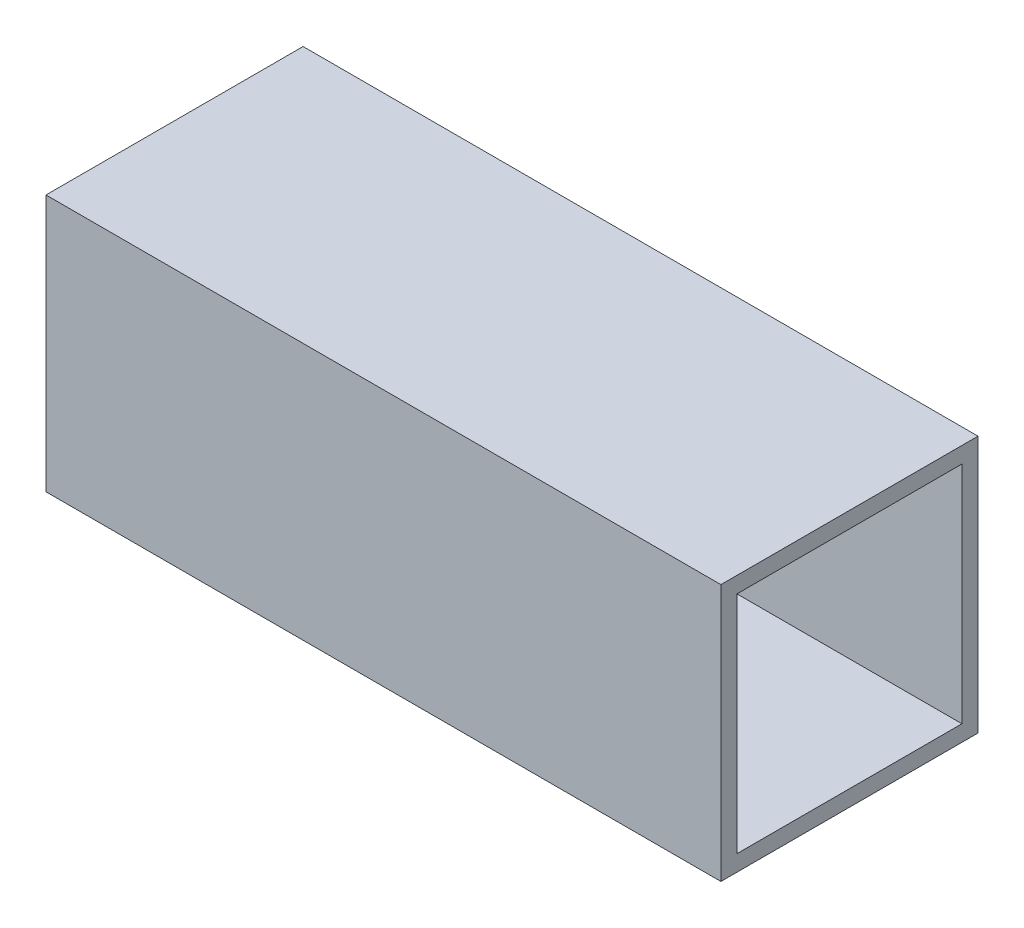
SolidWorks part; units mm, degrees
material "6061-T6 (SS)"
ref_plane "Front Plane" through (0, 0, 0) normal (0, 0, 1) x (1, 0, 0)
ref_plane "Top Plane" through (0, 0, 0) normal (0, 1, 0) x (1, 0, 0)
ref_plane "Right Plane" through (0, 0, 0) normal (1, 0, 0) x (0, 0, -1)
sketch "Sketch1" plane through (0, 0, 0) normal (1, 0, 0) x (0, 0, -1)
  line L1 (0, 0) -> (50.8, 0)
  line L2 (0, 0) -> (0, 50.8)
  line L3 (0, 50.8) -> (50.8, 50.8)
  line L4 (50.8, 0) -> (50.8, 50.8)
  dimension "D1" = 50.8
extrude "Boss-Extrude1" add sketch "Sketch1" along normal blind 133.35
shell "Shell1" thickness 3.175 removed face at (0, 25.4, -25.4) removed face at (133.35, 25.4, -25.4)
